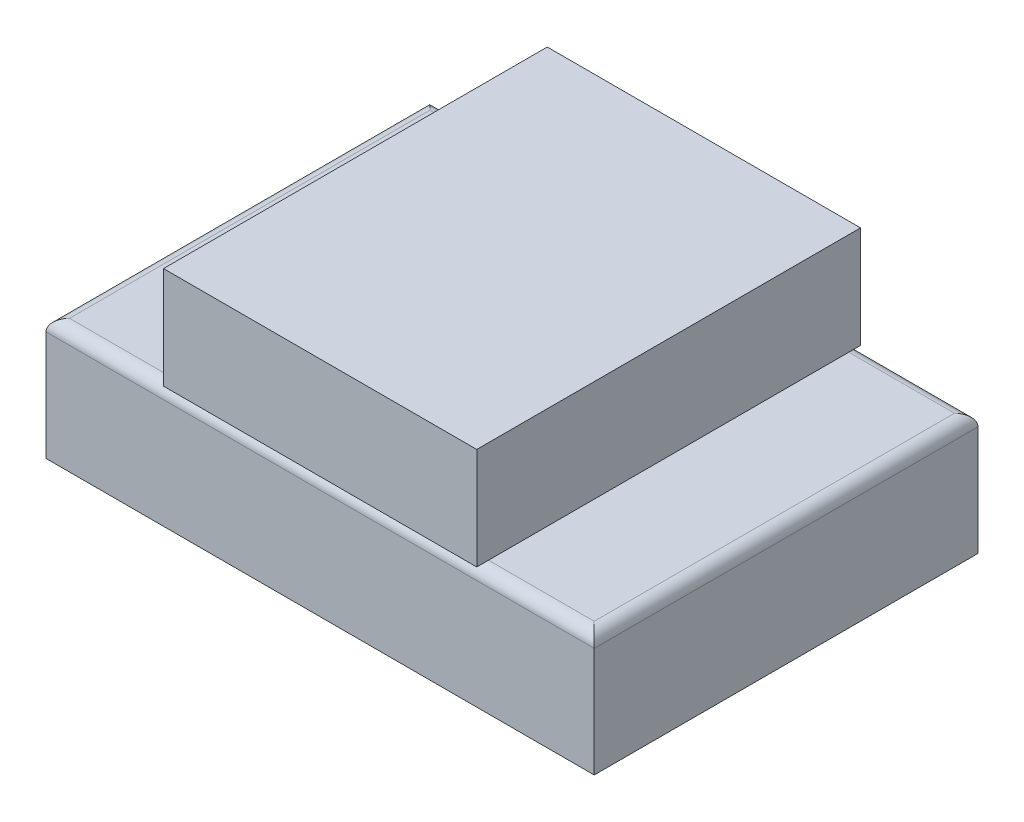
SolidWorks part; units mm, degrees
ref_plane "Front Plane" through (0, 0, 0) normal (0, 0, 1) x (1, 0, 0)
ref_plane "Top Plane" through (0, 0, 0) normal (0, 1, 0) x (1, 0, 0)
ref_plane "Right Plane" through (0, 0, 0) normal (1, 0, 0) x (0, 0, -1)
sketch "Sketch2" plane through (0, 0, 0) normal (0, 1, 0) x (1, 0, 0)
  line L0 (35, 22.5) -> (35, 24.5) construction
  line L1 (35, 24.5) -> (-35, 24.5)
  line L2 (35, 24.5) -> (35, -24.5)
  line L3 (35, -24.5) -> (-35, -24.5)
  line L4 (-35, 24.5) -> (-35, -24.5)
  line L5 (35, 24.5) -> (-35, -24.5) construction
  line L6 (35, -24.5) -> (-35, 24.5) construction
  line L7 (20, -24.5) -> (-20, -24.5)
  line L8 (20, -24.5) -> (20, 24.5)
  line L9 (20, 24.5) -> (-20, 24.5)
  line L10 (-20, -24.5) -> (-20, 24.5)
  line L11 (20, -24.5) -> (-20, 24.5) construction
  line L12 (20, 24.5) -> (-20, -24.5) construction
  line L13 (33, 24.5) -> (35, 24.5) construction
  line L14 (33, 26) -> (35, 26) construction
  line L15 (0, 24.5) -> (0, -24.5) construction
  line L16 (-35, 0) -> (35, 0) construction
  circle A0 centre (33, 22.5) radius 2
  circle A1 centre (33, 22.5) radius 3.5
  circle A4 centre (-33, -22.5) radius 2
  circle A5 centre (-33, -22.5) radius 3.5
  point P0 (0, 0)
  point P6 (0, 0)
  dimension "D4" = 0
  dimension "D6" = 7
  dimension "D7" = 4
  dimension "D8" = 7
  dimension "D9" = 4
  dimension "D1" = 70
  dimension "D2" = 49
  dimension "D3" = 40
  dimension "D5" = 0
extrude "Boss-Extrude1" add sketch "Sketch2" along normal blind 13 contours L10 L9 L8 L7
extrude "Boss-Extrude2" add sketch "Sketch2<3>" against normal blind 15.5 separate body contours L3 L4 L1 L2
sketch "Sketch2<3>" plane through (0, 0, 0) normal (0, 1, 0) x (1, 0, 0) same geometry as "Sketch2"
fillet "Fillet2" radius 1.5 4 edges at (-35, 0, 0) (0, 0, 24.5) (0, 0, -24.5) (35, 0, 0)
